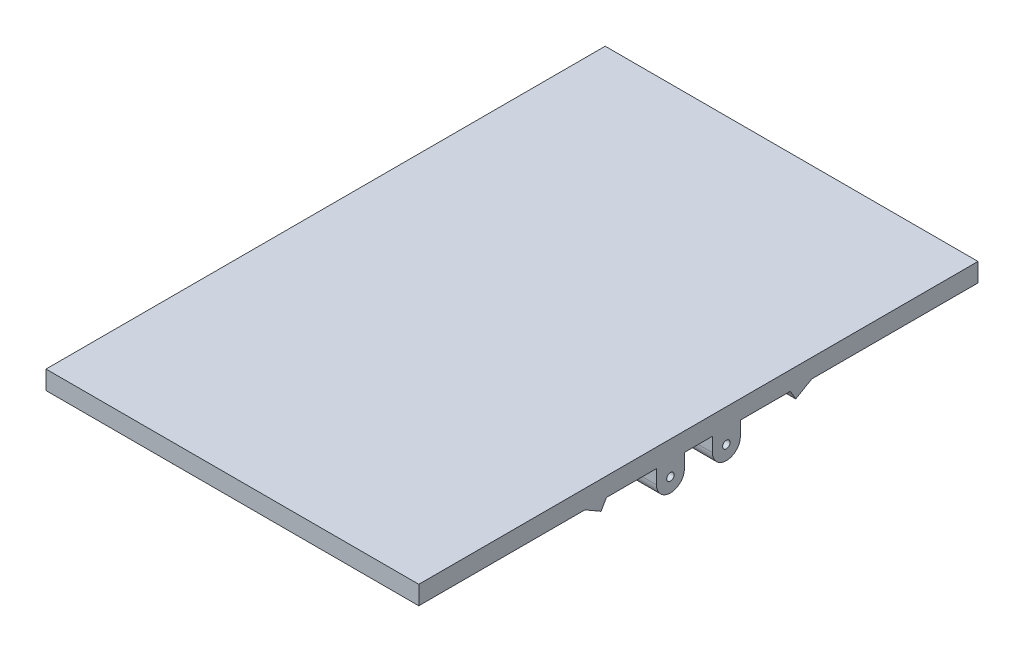
SolidWorks part; units mm, degrees
ref_plane "Front Plane" through (0, 0, 0) normal (0, 0, 1) x (1, 0, 0)
ref_plane "Top Plane" through (0, 0, 0) normal (0, 1, 0) x (1, 0, 0)
ref_plane "Right Plane" through (0, 0, 0) normal (1, 0, 0) x (0, 0, -1)
sketch "Sketch1" plane through (0, 0, 0) normal (0, 1, 0) x (1, 0, 0)
  line L1 (-200, -300) -> (200, -300)
  line L2 (-200, -300) -> (-200, 300)
  line L3 (-200, 300) -> (200, 300)
  line L4 (200, -300) -> (200, 300)
  line L5 (-200, -300) -> (200, 300) construction
  line L6 (-200, 300) -> (200, -300) construction
  point P0 (0, 0)
  dimension "D1" = 600
  dimension "D2" = 400
extrude "Boss-Extrude1" add sketch "Sketch1" along normal blind 20
sketch "Sketch3" plane through (200, 0, 0) normal (1, 0, 0) x (0, 0, -1)
  line L0 (-300, 0) -> (-30, 0) construction
  line L1 (-300, 0) -> (300, 0) construction
  line L2 (-30, 0) -> (-30, -15.1461) construction
  line L3 (-45, -15.1461) -> (-45, 0)
  line L4 (-45, 0) -> (-15, 0)
  line L5 (-15, 0) -> (-15, -15.1461)
  arc A0 (-45, -15.1461) -> (-15, -15.1461) centre (-30, -15.1461) ccw
  dimension "D2" = 15.1461
  dimension "D3" = 15
  dimension "D1" = 270
extrude "Boss-Extrude2" add sketch "Sketch3" against normal blind 30
mirror "Mirror1" about plane through (0, 0, 0) normal (0, 0, 1) of "Boss-Extrude2"
mirror "Mirror2" about plane through (0, 0, 0) normal (1, 0, 0) of "Mirror1", "Boss-Extrude2"
sketch "Sketch4" plane through (200, 0, 0) normal (1, 0, 0) x (0, 0, -1)
  line L0 (-121.7605, 0) -> (-104.44, -10)
  line L1 (-300, 0) -> (-45, 0) construction
  line L2 (-104.44, -10) -> (-98.6665, 0)
  line L3 (-98.6665, 0) -> (-121.7605, 0)
  dimension "D1" = 20
extrude "Boss-Extrude3" add sketch "Sketch4" against normal blind 40
mirror "Mirror3" about plane through (0, 0, 0) normal (0, 0, 1) of "Boss-Extrude3"
mirror "Mirror4" about plane through (0, 0, 0) normal (1, 0, 0) of "Boss-Extrude3", "Mirror3"
sketch "Sketch5" plane through (200, 0, 0) normal (1, 0, 0) x (0, 0, -1)
  circle A0 centre (-30, -15.1461) radius 4
  circle A1 centre (30, -15.1461) radius 4
  dimension "D1" = 8
extrude "Cut-Extrude1" cut sketch "Sketch5" against normal up to next
sketch "Sketch6" plane through (-200, 0, 0) normal (-1, 0, 0) x (0, 0, 1)
  circle A0 centre (-30, -15.1461) radius 4
  circle A1 centre (30, -15.1461) radius 4
  dimension "D1" = 8
extrude "Cut-Extrude2" cut sketch "Sketch6" against normal up to next
